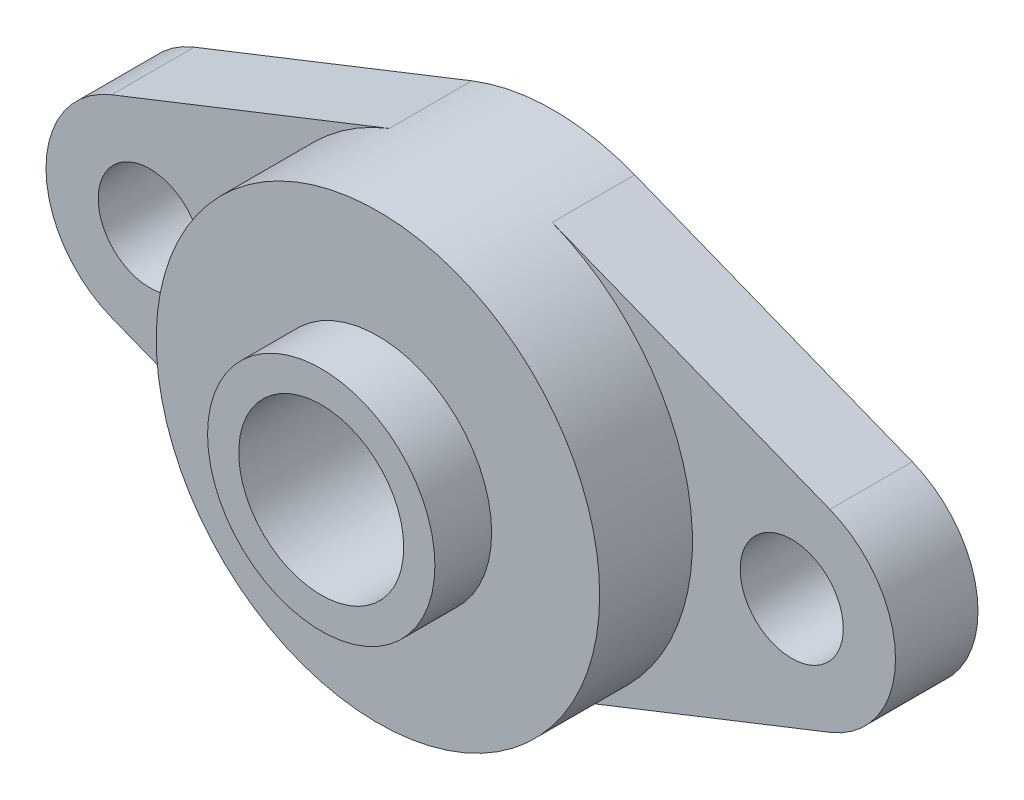
SolidWorks part; units mm, degrees
ref_plane "Front Plane" through (0, 0, 0) normal (0, 0, 1) x (1, 0, 0)
ref_plane "Top Plane" through (0, 0, 0) normal (0, 1, 0) x (1, 0, 0)
ref_plane "Right Plane" through (0, 0, 0) normal (1, 0, 0) x (0, 0, -1)
sketch "Sketch2" plane through (0, 0, 0) normal (0, 0, 1) x (1, 0, 0)
  line L0 (49.4109, 0) -> (-49.4109, 0) construction
  line L1 (65.3883, 0) -> (-65.3883, 0) construction
  line L2 (-55.2811, 14.8599) -> (-12.5401, 31.7441)
  line L3 (-55.2811, -14.8599) -> (-12.5401, -31.7441)
  line L4 (55.2811, -14.8599) -> (12.5401, -31.7441)
  line L5 (12.5401, 31.7441) -> (55.2811, 14.8599)
  circle A0 centre (0, 0) radius 12.7
  circle A1 centre (-49.4109, 0) radius 7.9375
  circle A2 centre (49.4109, 0) radius 7.9375
  arc A3 (12.5401, 31.7441) -> (-12.5401, 31.7441) centre (0, 0) ccw
  arc A4 (-12.5401, -31.7441) -> (12.5401, -31.7441) centre (0, 0) ccw
  arc A5 (-55.2811, 14.8599) -> (-55.2811, -14.8599) centre (-49.4109, 0) ccw
  arc A6 (55.2811, 14.8599) -> (55.2811, -14.8599) centre (49.4109, 0) cw
  point P6 (0, 0)
  point P14 (0, 0)
  point P20 (-65.3883, 0)
  point P23 (65.3883, 0)
  dimension "D1" = 25.4
  dimension "D2" = 15.875
  dimension "D3" = 15.875
  dimension "D4" = 34.1313
  dimension "D5" = 34.1313
  dimension "D6" = 98.8219
extrude "Boss-Extrude1" add sketch "Sketch2" along normal mid plane 12.7 contours A1 | A0 | A2 | L2 A3 L5 A6 L4 A4 L3 A5 region at (0, 0, 0) region at (-49.4109, 0, 0) region at (49.4109, 0, 0)
sketch "Sketch3" plane through (0, 0, 6.35) normal (0, 0, 1) x (1, 0, 0)
  circle A0 centre (0, 0) radius 34.1312
  arc A1 (12.5401, 31.7441) -> (-12.5401, 31.7441) centre (0, 0) ccw construction
  arc A2 (12.5401, 31.7441) -> (-12.5401, 31.7441) centre (0, 0) ccw
  circle A3 centre (0, 0) radius 12.7 construction
  circle A4 centre (0, 0) radius 12.7
  point P3 (0, 0)
  circle M2 centre (0, 0) radius 12.7
extrude "Boss-Extrude2" add sketch "Sketch3" along normal blind 14.2875 contours M2 | A0 region at (0, 0, 6.35)
sketch "Sketch4" plane through (0, 0, 20.6375) normal (0, 0, 1) x (1, 0, 0)
  circle A0 centre (0, 0) radius 17.5
  circle A1 centre (0, 0) radius 12.7 construction
  circle A2 centre (0, 0) radius 12.7
  circle M2 centre (0, 0) radius 12.7
  dimension "D1" = 35
extrude "Boss-Extrude3" add sketch "Sketch4" along normal blind 8.7312 contours M2 | A0 region at (0, 0, 20.6375)
